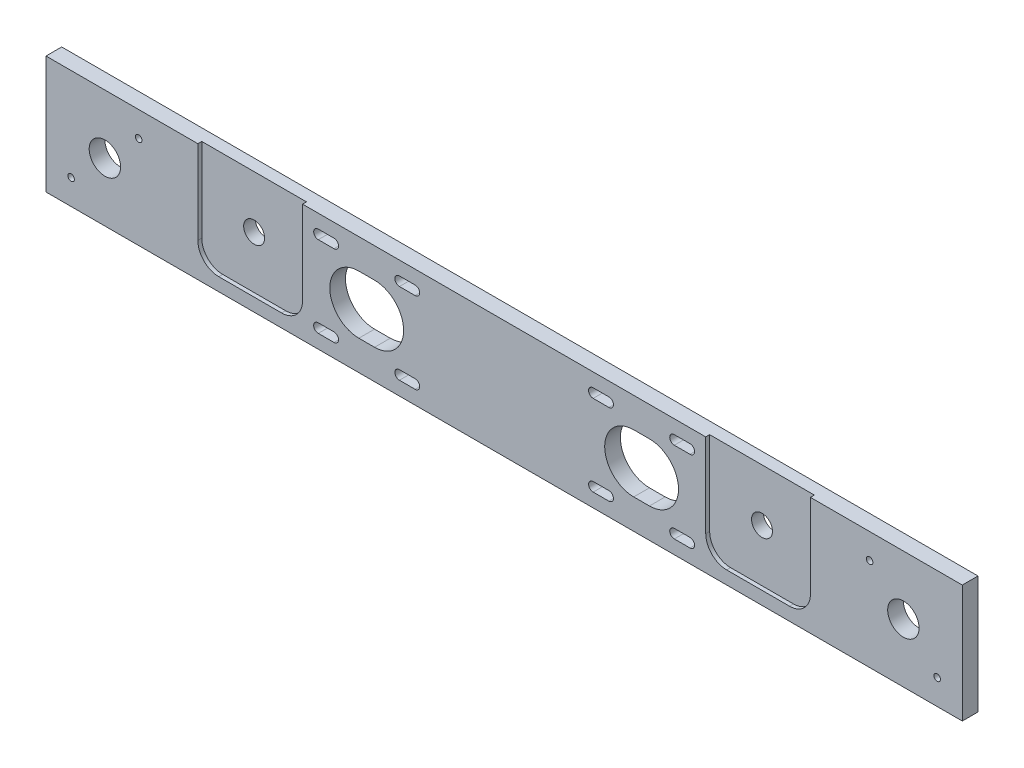
SolidWorks part; units mm, degrees
ref_plane "Alzado" through (0, 0, 0) normal (0, 0, 1) x (1, 0, 0)
ref_plane "Planta" through (0, 0, 0) normal (0, 1, 0) x (1, 0, 0)
ref_plane "Vista lateral" through (0, 0, 0) normal (1, 0, 0) x (0, 0, -1)
sketch "Croquis1" plane through (0, 0, 0) normal (0, 0, 1) x (1, 0, 0)
  line L1 (-350, -45) -> (0, -45)
  line L2 (-350, -45) -> (-350, 0)
  line L3 (-350, 0) -> (0, 0)
  line L4 (0, -45) -> (0, 0)
  dimension "D1" = 350
  dimension "D2" = 45
extrude "Saliente-Extruir1" add sketch "Croquis1" along normal blind 6 contours L3 L4 L1 L2
sketch "Croquis2" plane through (0, 0, 6) normal (0, 0, 1) x (1, 0, 0)
  line L0 (-350, -45) -> (-350, 0) construction
  line L1 (0, -45) -> (0, 0) construction
  line L2 (-350, -45) -> (0, -45) construction
  line L3 (-340.4047, -35.4047) -> (-314.5953, -9.5953) construction
  line L4 (-35.4047, -9.5953) -> (-9.5953, -35.4047) construction
  line L5 (-350, 0) -> (0, 0) construction
  circle A0 centre (-327.5, -22.5) radius 6
  circle A1 centre (-22.5, -22.5) radius 6
  circle A2 centre (-327.5, -22.5) radius 18.25 construction
  circle A4 centre (-314.5953, -9.5953) radius 1.25
  circle A5 centre (-340.4047, -35.4047) radius 1.25
  circle A6 centre (-22.5, -22.5) radius 18.25 construction
  circle A7 centre (-35.4047, -9.5953) radius 1.25
  circle A8 centre (-9.5953, -35.4047) radius 1.25
  circle A9 centre (-22.5, -22.5) radius 21 construction
  circle A10 centre (-327.5, -22.5) radius 21 construction
  dimension "D1" = 12
  dimension "D2" = 12
  dimension "D7" = 36.5
  dimension "D9" = 2.5
  dimension "D10" = 2.5
  dimension "D11" = 36.5
  dimension "D13" = 2.5
  dimension "D14" = 2.5
  dimension "D15" = 42
  dimension "D16" = 42
  dimension "D3" = 22.5
  dimension "D4" = 22.5
  dimension "D5" = 22.5
  dimension "D6" = 22.5
  dimension "D8" = 45
  dimension "D12" = 45
extrude "Cortar-Extruir1" cut sketch "Croquis2" against normal through all
sketch "Croquis3" plane through (0, 0, 6) normal (0, 0, 1) x (1, 0, 0)
  line L2 (-246, -7) -> (-240, -7) construction
  line L3 (-141, -7) -> (-135, -7) construction
  line L4 (-141, -5.25) -> (-135, -5.25)
  line L5 (-141, -8.75) -> (-135, -8.75)
  line L6 (-125.5, -22.5) -> (-119.5, -22.5) construction
  line L7 (-125.5, -11.4) -> (-119.5, -11.4)
  line L8 (-125.5, -33.6) -> (-119.5, -33.6)
  line L9 (-350, 0) -> (0, 0) construction
  line L10 (-141, -38) -> (-135, -38) construction
  line L11 (-141, -36.25) -> (-135, -36.25)
  line L12 (-141, -39.75) -> (-135, -39.75)
  line L13 (-110, -7) -> (-104, -7) construction
  line L14 (-110, -5.25) -> (-104, -5.25)
  line L15 (-110, -8.75) -> (-104, -8.75)
  line L16 (-110, -38) -> (-104, -38) construction
  line L17 (-110, -36.25) -> (-104, -36.25)
  line L18 (-110, -39.75) -> (-104, -39.75)
  line L19 (-246, -5.25) -> (-240, -5.25)
  line L20 (-246, -8.75) -> (-240, -8.75)
  line L21 (-230.5, -22.5) -> (-224.5, -22.5) construction
  line L22 (-230.5, -11.4) -> (-224.5, -11.4)
  line L23 (-230.5, -33.6) -> (-224.5, -33.6)
  line L24 (-246, -38) -> (-240, -38) construction
  line L25 (-246, -36.25) -> (-240, -36.25)
  line L26 (-246, -39.75) -> (-240, -39.75)
  line L27 (-215, -7) -> (-209, -7) construction
  line L28 (-215, -5.25) -> (-209, -5.25)
  line L29 (-215, -8.75) -> (-209, -8.75)
  line L30 (-215, -38) -> (-209, -38) construction
  line L31 (-215, -36.25) -> (-209, -36.25)
  line L32 (-215, -39.75) -> (-209, -39.75)
  line L33 (-350, 0) -> (0, 0) construction
  arc A2 (-246, -5.25) -> (-246, -8.75) centre (-246, -7) ccw
  arc A5 (-141, -5.25) -> (-141, -8.75) centre (-141, -7) ccw
  arc A6 (-135, -8.75) -> (-135, -5.25) centre (-135, -7) ccw
  arc A7 (-125.5, -11.4) -> (-125.5, -33.6) centre (-125.5, -22.5) ccw
  arc A8 (-119.5, -33.6) -> (-119.5, -11.4) centre (-119.5, -22.5) ccw
  circle A9 centre (-22.5, -22.5) radius 6 construction
  arc A11 (-141, -36.25) -> (-141, -39.75) centre (-141, -38) ccw
  arc A12 (-135, -39.75) -> (-135, -36.25) centre (-135, -38) ccw
  arc A13 (-110, -5.25) -> (-110, -8.75) centre (-110, -7) ccw
  arc A14 (-104, -8.75) -> (-104, -5.25) centre (-104, -7) ccw
  arc A15 (-110, -36.25) -> (-110, -39.75) centre (-110, -38) ccw
  arc A16 (-104, -39.75) -> (-104, -36.25) centre (-104, -38) ccw
  arc A17 (-240, -8.75) -> (-240, -5.25) centre (-240, -7) ccw
  arc A18 (-230.5, -11.4) -> (-230.5, -33.6) centre (-230.5, -22.5) ccw
  arc A19 (-224.5, -33.6) -> (-224.5, -11.4) centre (-224.5, -22.5) ccw
  arc A20 (-246, -36.25) -> (-246, -39.75) centre (-246, -38) ccw
  arc A21 (-240, -39.75) -> (-240, -36.25) centre (-240, -38) ccw
  arc A22 (-215, -5.25) -> (-215, -8.75) centre (-215, -7) ccw
  arc A23 (-209, -8.75) -> (-209, -5.25) centre (-209, -7) ccw
  arc A24 (-215, -36.25) -> (-215, -39.75) centre (-215, -38) ccw
  arc A25 (-209, -39.75) -> (-209, -36.25) centre (-209, -38) ccw
  circle A26 centre (-327.5, -22.5) radius 6 construction
  point P2 (-122.5, -22.5)
  point P12 (-138, -7)
  point P20 (-227.5, -22.5)
  point P23 (-138, -38)
  point P30 (-107, -7)
  point P37 (-107, -38)
  point P48 (-243, -7)
  point P55 (-243, -38)
  point P62 (-212, -7)
  point P69 (-212, -38)
  dimension "D5" = 1.75
  dimension "D4" = 22.2
  dimension "D9" = 15.5
  dimension "D18" = 1.75
  dimension "D19" = 1.75
  dimension "D20" = 1.75
  dimension "D21" = 1.75
  dimension "D36" = 1.75
  dimension "D37" = 1.75
  dimension "D38" = 1.75
  dimension "D1" = 100
  dimension "D2" = 22.5
  dimension "D3" = 6
  dimension "D6" = 15.5
  dimension "D7" = 6
  dimension "D8" = 15.5
  dimension "D10" = 15.5
  dimension "D11" = 15.5
  dimension "D12" = 15.5
  dimension "D13" = 6
  dimension "D14" = 6
  dimension "D15" = 6
  dimension "D16" = 15.5
  dimension "D17" = 15.5
  dimension "D22" = 6
  dimension "D23" = 6
  dimension "D24" = 22.2
  dimension "D25" = 15.5
  dimension "D26" = 15.5
  dimension "D27" = 15.5
  dimension "D28" = 15.5
  dimension "D29" = 15.5
  dimension "D30" = 15.5
  dimension "D31" = 6
  dimension "D32" = 6
  dimension "D33" = 6
  dimension "D34" = 15.5
  dimension "D35" = 15.5
  dimension "D39" = 100
  dimension "D40" = 22.5
extrude "Cortar-Extruir2" cut sketch "Croquis3" against normal through all
sketch "Croquis5" plane through (0, 0, 6) normal (0, 0, 1) x (1, 0, 0)
  line L0 (-350, 0) -> (0, 0) construction
  line L1 (-292, 0) -> (-252, 0)
  line L2 (-292, 0) -> (-292, -32)
  line L3 (-284, -40) -> (-260, -40)
  line L4 (-252, 0) -> (-252, -32)
  line L5 (-350, -45) -> (-350, 0) construction
  line L6 (-98, 0) -> (-58, 0)
  line L7 (-98, 0) -> (-98, -32)
  line L8 (-90, -40) -> (-66, -40)
  line L9 (-58, 0) -> (-58, -32)
  line L10 (0, -45) -> (0, 0) construction
  arc A0 (-260, -40) -> (-252, -32) centre (-260, -32) ccw
  arc A1 (-284, -40) -> (-292, -32) centre (-284, -32) cw
  arc A2 (-66, -40) -> (-58, -32) centre (-66, -32) ccw
  arc A3 (-90, -40) -> (-98, -32) centre (-90, -32) cw
  point P4 (-300.4292, 0)
  point P11 (-252, -40)
  point P24 (0, 0)
  point P25 (-58, 0)
  dimension "D4" = 8
  dimension "D6" = 8
  dimension "D1" = 40
  dimension "D2" = 58
  dimension "D3" = 40
  dimension "D5" = 40
  dimension "D7" = 58
  dimension "D8" = 40
extrude "Cortar-Extruir4" cut sketch "Croquis5" against normal blind 1.5
sketch "Croquis7" plane through (0, 0, 4.5) normal (0, 0, 1) x (1, 0, 0)
  line L0 (-252, -32) -> (-252, 0) construction
  line L1 (-252, 0) -> (-292, 0) construction
  line L3 (-58, -32) -> (-58, 0) construction
  line L4 (-58, 0) -> (-98, 0) construction
  circle A0 centre (-272, -20) radius 4
  circle A1 centre (-78, -20) radius 4
  point P6 (0, 0)
  point P9 (-78, -20)
  dimension "D1" = 8
  dimension "D4" = 8
  dimension "D5" = 20
  dimension "D2" = 20
  dimension "D3" = 20
  dimension "D6" = 20
extrude "Cortar-Extruir5" cut sketch "Croquis7" against normal through all
